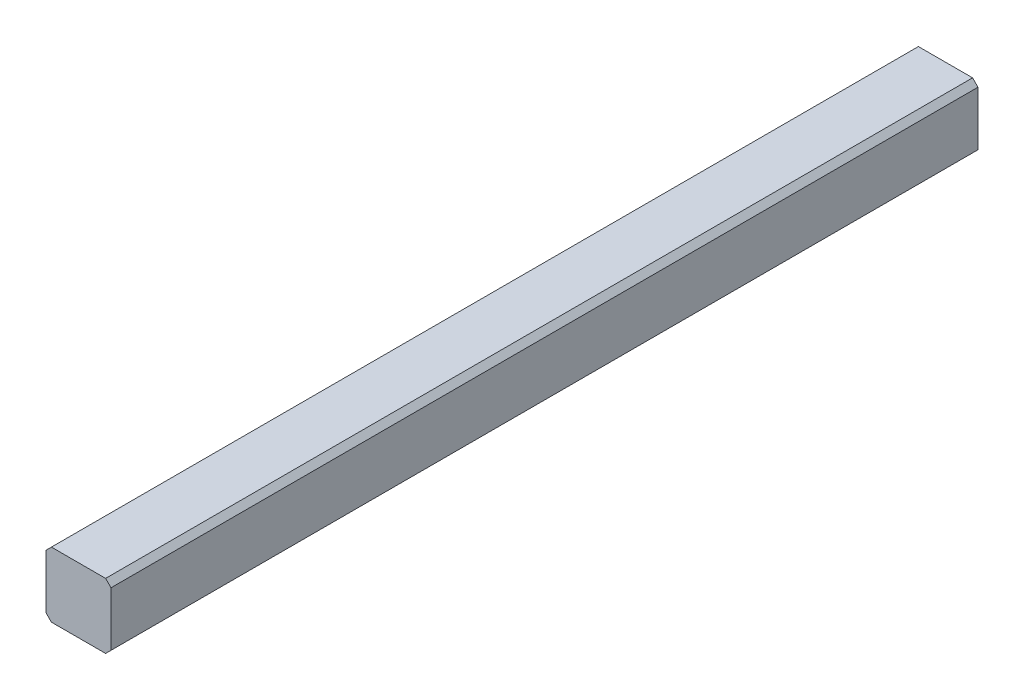
SolidWorks part; units mm, degrees
ref_plane "Front" through (0, 0, 0) normal (0, 0, 1) x (1, 0, 0)
ref_plane "Top" through (0, 0, 0) normal (0, 1, 0) x (1, 0, 0)
ref_plane "Right" through (0, 0, 0) normal (1, 0, 0) x (0, 0, -1)
sketch "Esquisse1" plane through (0, 0, 0) normal (0, 0, 1) x (1, 0, 0)
  line L1 (0, 0) -> (60, 0)
  line L2 (0, 0) -> (0, 60)
  line L3 (0, 60) -> (60, 60)
  line L4 (60, 0) -> (60, 60)
  dimension "D1" = 60
  dimension "D2" = 60
extrude "Boss.-Extru.1" add sketch "Esquisse1" along normal blind 800
sketch "Esquisse2" plane through (0, 0, 0) normal (0, -1, 0) x (1, 0, 0)
  line L0 (30, 0) -> (30, 160) construction
  line L1 (0, 0) -> (60, 0) construction
  line L2 (30, 175) -> (30, 145) construction
  line L3 (38, 175) -> (38, 145)
  line L4 (22, 175) -> (22, 145)
  line L5 (30, 800) -> (30, 740) construction
  line L6 (0, 800) -> (60, 800) construction
  line L7 (30, 725) -> (30, 755) construction
  line L8 (22, 725) -> (22, 755)
  line L9 (38, 725) -> (38, 755)
  arc A0 (38, 175) -> (22, 175) centre (30, 175) ccw
  arc A1 (22, 145) -> (38, 145) centre (30, 145) ccw
  arc A2 (22, 725) -> (38, 725) centre (30, 725) ccw
  arc A3 (38, 755) -> (22, 755) centre (30, 755) ccw
  point P6 (30, 160)
  point P17 (30, 740)
  dimension "D1" = 16
  dimension "D2" = 30
  dimension "D3" = 160
  dimension "D4" = 60
extrude "Enlèv. mat.-Extru.1" cut sketch "Esquisse2" against normal blind 30
sketch "Esquisse3" plane through (60, 0, 0) normal (1, 0, 0) x (0, 0, -1)
  line L0 (0, 30) -> (-160, 30) construction
  line L1 (0, 0) -> (0, 60) construction
  line L2 (-175, 30) -> (-145, 30) construction
  line L3 (-175, 38) -> (-145, 38)
  line L4 (-175, 22) -> (-145, 22)
  line L5 (-800, 30) -> (-740, 30) construction
  line L6 (-800, 0) -> (-800, 60) construction
  line L7 (-755, 30) -> (-725, 30) construction
  line L8 (-755, 38) -> (-725, 38)
  line L9 (-755, 22) -> (-725, 22)
  arc A0 (-175, 38) -> (-175, 22) centre (-175, 30) ccw
  arc A1 (-145, 22) -> (-145, 38) centre (-145, 30) ccw
  arc A2 (-755, 38) -> (-755, 22) centre (-755, 30) ccw
  arc A3 (-725, 22) -> (-725, 38) centre (-725, 30) ccw
  point P6 (-160, 30)
  point P17 (-740, 30)
  dimension "D1" = 16
  dimension "D2" = 30
  dimension "D3" = 160
  dimension "D4" = 60
extrude "Enlèv. mat.-Extru.2" [suppressed] cut sketch "Esquisse3" against normal blind 30
extrude "Enlèv. mat.-Extru.3" cut sketch "Esquisse3<2>" along normal blind 30 from vertex starting at point (0, 0, 0)
sketch "Esquisse3<2>" plane through (60, 0, 0) normal (1, 0, 0) x (0, 0, -1) same geometry as "Esquisse3"
chamfer "Chanfrein1" distance 5 angle 45 4 edges at (0, 60, 400) (60, 60, 400) (60, 0, 400) (0, 0, 400)
sketch "Esquisse5" [suppressed] plane through (0, 0, 0) normal (0, -1, 0) x (1, 0, 0)
  line L0 (60, 1000) -> (60, 620) construction
  line L1 (5, 1000) -> (75, 1000) construction
  line L3 (80, 1000) -> (80, 0) construction
  circle A0 centre (60, 620) radius 5
  dimension "D1" = 10
  dimension "D2" = 380
  dimension "D3" = 20
extrude "Enlèv. mat.-Extru.5" [suppressed] cut sketch "Esquisse5" against normal blind 20
